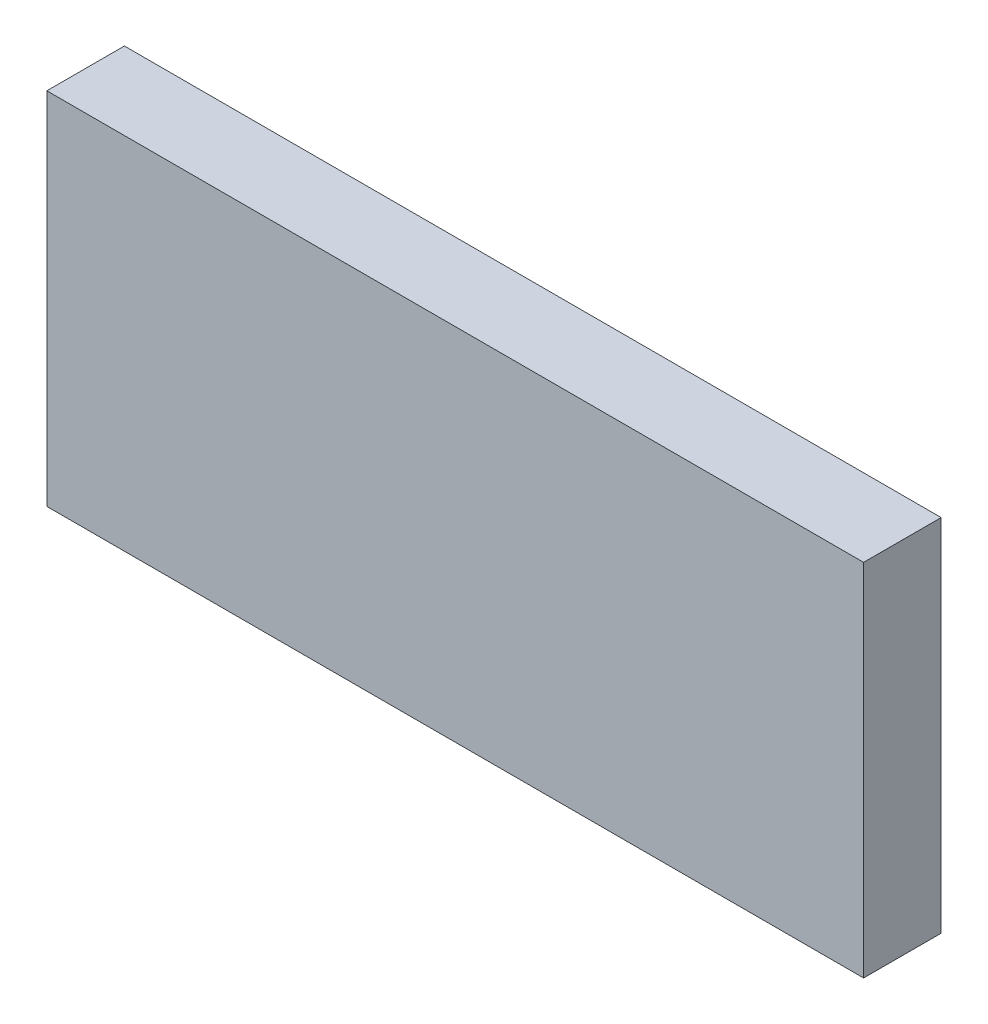
SolidWorks part; units mm, degrees
ref_plane "Plan de face" through (0, 0, 0) normal (0, 0, 1) x (1, 0, 0)
ref_plane "Plan de dessus" through (0, 0, 0) normal (0, 1, 0) x (1, 0, 0)
ref_plane "Plan de droite" through (0, 0, 0) normal (1, 0, 0) x (0, 0, -1)
sketch "Esquisse1" plane through (0, 0, 0) normal (0, 0, 1) x (1, 0, 0)
  line L1 (-36.702, 21.4105) -> (26.488, 21.4105)
  line L2 (-36.702, 21.4105) -> (-36.702, -6.4395)
  line L3 (-36.702, -6.4395) -> (26.488, -6.4395)
  line L4 (26.488, 21.4105) -> (26.488, -6.4395)
  dimension "D1" = 63.19
  dimension "D2" = 27.85
extrude "Boss.-Extru.1" add sketch "Esquisse1" along normal blind 6
